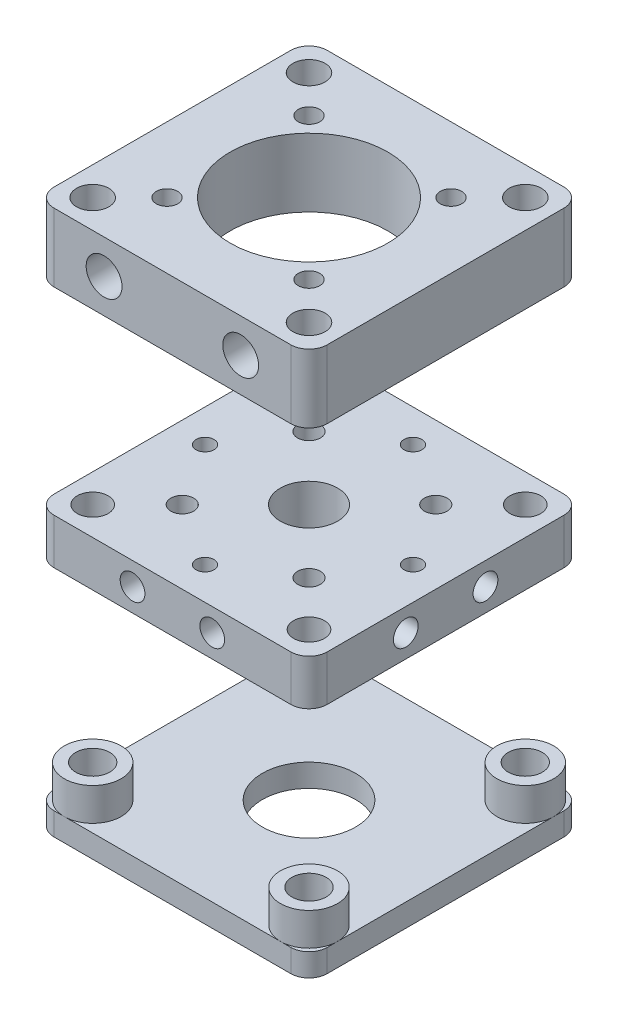
SolidWorks part; units mm, degrees
material "Alum Plate"
ref_plane "Front Plane" through (0, 0, 0) normal (0, 0, 1) x (1, 0, 0)
ref_plane "Top Plane" through (0, 0, 0) normal (0, 1, 0) x (1, 0, 0)
ref_plane "Right Plane" through (0, 0, 0) normal (1, 0, 0) x (0, 0, -1)
other "Bounding Box"
ref_plane "Default Plane" through (-8.9266, -12.7485, 0) normal (-0.1736, 0.9848, 0) x (0.9848, 0.1736, 0)
sketch "Sketch1" plane through (0, 0, 0) normal (0, 1, 0) x (1, 0, 0)
  line L0 (0, -12.5) -> (0, 12.5) construction
  line L1 (-14.5, 0) -> (0, 14.5) construction
  line L2 (-19.05, 19.05) -> (19.05, 19.05)
  line L3 (-19.05, 19.05) -> (-19.05, -19.05)
  line L4 (-19.05, -19.05) -> (19.05, -19.05)
  line L5 (19.05, 19.05) -> (19.05, -19.05)
  line L6 (-19.05, 19.05) -> (19.05, -19.05) construction
  line L7 (-19.05, -19.05) -> (19.05, 19.05) construction
  line L8 (8.8388, 8.8388) -> (-8.8388, 8.8388) construction
  line L9 (8.8388, 8.8388) -> (8.8388, -8.8388) construction
  line L10 (8.8388, -8.8388) -> (-8.8388, -8.8388) construction
  line L11 (-8.8388, 8.8388) -> (-8.8388, -8.8388) construction
  line L12 (8.8388, 8.8388) -> (-8.8388, -8.8388) construction
  line L13 (8.8388, -8.8388) -> (-8.8388, 8.8388) construction
  line L14 (-14.5, 0) -> (0, -14.5) construction
  line L15 (0, 14.5) -> (14.5, 0) construction
  line L16 (0, -14.5) -> (14.5, 0) construction
  line L17 (-14.5, 0) -> (14.5, 0) construction
  line L18 (0, 14.5) -> (0, -14.5) construction
  circle A0 centre (-15.24, 15.24) radius 1.3843 construction
  circle A1 centre (15.24, 15.24) radius 1.3843 construction
  circle A2 centre (15.24, -15.24) radius 1.3843 construction
  circle A3 centre (-15.24, -15.24) radius 1.3843 construction
  circle A4 centre (0, 0) radius 4
  circle A5 centre (8.8388, 8.8388) radius 1.5875
  circle A6 centre (8.8388, -8.8388) radius 1.5875
  circle A7 centre (-8.8388, -8.8388) radius 1.5875
  circle A8 centre (-8.8388, 8.8388) radius 1.5875
  circle A9 centre (-14.5, 0) radius 1.25
  circle A10 centre (0, 14.5) radius 1.25
  circle A11 centre (14.5, 0) radius 1.25
  circle A12 centre (0, -14.5) radius 1.25
  point P3 (0, 0)
  circle B0 centre (-9.8995, -9.8995) radius 1.2645 construction
  circle B1 centre (0, -8) radius 1.5875 construction
  circle B2 centre (0, 0) radius 4 construction
  circle B3 centre (9.8995, 9.8995) radius 1.2645 construction
  circle B4 centre (0, 8) radius 1.5875 construction
  circle B5 centre (9.8995, -9.8995) radius 1.2645 construction
  circle B6 centre (0, -12.5) radius 1.5875 construction
  circle B7 centre (-9.5, 0) radius 1.5875 construction
  circle B8 centre (-15.24, 15.24) radius 1.3843 construction
  circle B9 centre (15.24, 15.24) radius 1.3843 construction
  circle B10 centre (15.24, -15.24) radius 1.3843 construction
  circle B11 centre (-15.24, -15.24) radius 1.3843 construction
  circle B12 centre (9.5, 0) radius 1.5875 construction
  circle B13 centre (-9.8995, 9.8995) radius 1.2645 construction
  circle B14 centre (0, 12.5) radius 1.5875 construction
  dimension "D2" = 3.175
  dimension "D4" = 2.5
  dimension "D1" = 38.1
  dimension "D3" = 25
  dimension "D5" = 29
sketch_block_instance "Block-36mm gearbox motor block holes-1"
sketch_block "Block-36mm gearbox motor block holes"
extrude "Boss-Extrude1" add sketch "Sketch1" along normal mid plane 6.35 contours L5 L2 L3 L4 A12 A11 A9 A8 A10 A7 A6 A5 A4 A3 A2 A1 A0 region at (0, 0, -18.5112)
sketch "Sketch4" plane through (0, 0, 19.05) normal (0, 0, 1) x (1, 0, 0)
  line L0 (-5.5562, 0) -> (0, 0) construction
  line L1 (0, 0) -> (5.5562, 0) construction
  circle A0 centre (-5.5562, 0) radius 1.7272
  circle A1 centre (5.5562, 0) radius 1.7272
  dimension "D2" = 3.4544
  dimension "D1" = 11.1125
extrude "Cut-Extrude2" cut sketch "Sketch4" against normal blind 10.795
sketch "Sketch7" plane through (0, -3.175, 0) normal (0, -1, 0) x (1, 0, 0)
  line L0 (-19.05, 15.0813) -> (-15.0813, 15.0813) construction
  line L1 (-19.05, -19.05) -> (-19.05, 19.05) construction
  line L2 (-15.0813, 15.0813) -> (-15.0813, 19.05) construction
  line L3 (-19.05, 19.05) -> (19.05, 19.05) construction
  line L4 (0, 0) -> (-15.0813, 15.0813) construction
  line L5 (0, 0) -> (15.0813, 15.0812) construction
  circle A0 centre (-15.0813, 15.0813) radius 2.1526
  circle A1 centre (15.0813, 15.0812) radius 2.1527
  circle A2 centre (15.0812, -15.0813) radius 2.1527
  circle A3 centre (-15.0813, -15.0812) radius 2.1526
  dimension "D2" = 4.3053
  dimension "D1" = 3.9688
  dimension "D4" = 90
  dimension "D3" = 4
extrude "Cut-Extrude3" cut sketch "Sketch7" against normal through all
pattern_circular "CirPattern1" count 4 over 360 about axis through (0, 3.175, 0) along (0, -1, 0) of "Cut-Extrude2"
ref_plane "Plane1" through (0, -32.512, 0) normal (0, -1, 0) x (-1, 0, 0)
sketch "Sketch6" plane through (0, -32.512, 0) normal (0, -1, 0) x (-1, 0, 0)
  line L0 (19.05, 19.05) -> (-19.05, 19.05) construction
  line L1 (19.05, 19.05) -> (19.05, -19.05) construction
  line L2 (19.05, -19.05) -> (-19.05, -19.05) construction
  line L3 (-19.05, 19.05) -> (-19.05, -19.05) construction
  line L12 (19.05, 19.05) -> (-19.05, 19.05)
  line L13 (19.05, 19.05) -> (19.05, -19.05)
  line L14 (19.05, -19.05) -> (-19.05, -19.05)
  line L15 (-19.05, 19.05) -> (-19.05, -19.05)
  circle A8 centre (0, 0) radius 6.5
  circle A17 centre (-15.0812, 15.0813) radius 2.1526
  circle A18 centre (15.0813, 15.0812) radius 2.1526
  circle A19 centre (15.0813, -15.0813) radius 2.1527
  circle A20 centre (-15.0813, -15.0812) radius 2.1526
  circle A21 centre (-15.0812, 15.0813) radius 2.1527 construction
  dimension "D2" = 13
extrude "Boss-Extrude2" add sketch "Sketch6" along normal blind 3.175 separate body
fillet "Fillet1" radius 2.54 4 edges at (-19.05, 0, 19.05) (-19.05, 0, -19.05) (19.05, 0, -19.05) (19.05, 0, 19.05)
fillet "Fillet2" radius 2.54 4 edges at (-19.05, -34.0995, 19.05) (-19.05, -34.0995, -19.05) (19.05, -34.0995, -19.05) (19.05, -34.0995, 19.05)
sketch "Sketch8" plane through (0, -32.512, 0) normal (0, 1, 0) x (1, 0, 0)
  line L0 (-16.51, 19.05) -> (16.51, 19.05) construction
  circle A0 centre (-15.0813, 15.0812) radius 2.3876
  circle A1 centre (-15.0813, 15.0812) radius 3.9688
  dimension "D1" = 4.7752
extrude "Boss-Extrude3" add sketch "Sketch8" along normal offset from surface (4.572 mm away) 24.765 separate body up to face at (-15.0813, -3.175, -17.2339)
pattern_circular "CirPattern2" count 4 over 360 about axis through (0, -35.687, 0) along (0, 1, 0) of bodies 110
delete or keep bodies "Body-Delete/Keep 1" [suppressed] type keep bodies bodies 108
delete or keep bodies "Body-Delete/Keep 2" [suppressed] type keep bodies bodies 107
delete or keep bodies "Body-Delete/Keep 3" [suppressed] bodies 113
delete or keep bodies "Body-Delete/Keep 4" [suppressed] type delete bodies bodies 107
sketch "Sketch9" plane through (0, 3.175, 0) normal (0, 1, 0) x (1, 0, 0)
  line L0 (-16.51, -19.05) -> (16.51, -19.05) construction
  line L1 (-19.05, 19.05) -> (19.05, 19.05)
  line L2 (-19.05, 19.05) -> (-19.05, -19.05)
  line L3 (-19.05, -19.05) -> (19.05, -19.05)
  line L4 (19.05, 19.05) -> (19.05, -19.05)
  line L5 (-19.05, 19.05) -> (19.05, -19.05) construction
  line L6 (-19.05, -19.05) -> (19.05, 19.05) construction
  point P0 (0, 0)
extrude "Boss-Extrude4" add sketch "Sketch9" along normal blind 9.525 from offset 27.559 separate body
sketch "Sketch12" plane through (0, 0, -19.05) normal (0, 0, -1) x (-1, 0, 0)
  line L0 (-19.05, 35.4965) -> (-9.525, 35.4965) construction
  line L1 (-19.05, 40.259) -> (-19.05, 30.734) construction
  line L2 (-9.525, 35.4965) -> (9.525, 35.4965) construction
  line L3 (9.525, 35.4965) -> (19.05, 35.4965) construction
  line L4 (19.05, 40.259) -> (19.05, 30.734) construction
  circle A0 centre (-9.525, 35.4965) radius 2.5
  circle A1 centre (9.525, 35.4965) radius 2.5
  dimension "D2" = 5
  dimension "D1" = 19.05
extrude "Cut-Extrude5" cut sketch "Sketch12" against normal blind 9.525
mirror "Mirror1" about plane through (0, 0, 0) normal (0, 0, 1) of "Cut-Extrude5"
fillet "Fillet3" radius 2.54 4 edges at (19.05, 35.4965, -19.05) (19.05, 35.4965, 19.05) (-19.05, 35.4965, 19.05) (-19.05, 35.4965, -19.05)
sketch "Sketch10" plane through (0, 40.259, 0) normal (0, 1, 0) x (1, 0, 0)
  line L1 (-9.8995, 9.8995) -> (9.8995, 9.8995) construction
  line L2 (-9.8995, 9.8995) -> (-9.8995, -9.8995) construction
  line L3 (-9.8995, -9.8995) -> (9.8995, -9.8995) construction
  line L4 (9.8995, 9.8995) -> (9.8995, -9.8995) construction
  line L5 (-9.8995, 9.8995) -> (9.8995, -9.8995) construction
  line L6 (-9.8995, -9.8995) -> (9.8995, 9.8995) construction
  line L7 (-15.0813, 15.0812) -> (15.0813, 15.0812) construction
  line L8 (-15.0813, 15.0812) -> (-15.0813, -15.0813) construction
  line L9 (-15.0813, -15.0813) -> (15.0813, -15.0813) construction
  line L10 (15.0813, 15.0812) -> (15.0813, -15.0813) construction
  line L11 (-15.0813, 15.0812) -> (15.0813, -15.0813) construction
  line L12 (-15.0813, -15.0813) -> (15.0813, 15.0812) construction
  circle A0 centre (0, 0) radius 11
  circle A1 centre (-9.8995, 9.8995) radius 1.5
  circle A2 centre (9.8995, 9.8995) radius 1.5
  circle A3 centre (9.8995, -9.8995) radius 1.5
  circle A4 centre (-9.8995, -9.8995) radius 1.5
  circle A5 centre (-15.0813, -15.0813) radius 2.2479
  circle A6 centre (-15.0813, 15.0812) radius 2.2479
  circle A7 centre (15.0813, 15.0812) radius 2.2479
  circle A8 centre (15.0813, -15.0813) radius 2.2479
  dimension "D2" = 22
  dimension "D4" = 4.4958
  dimension "D5" = 3
  dimension "D1" = 28
  dimension "D3" = 30.1625
extrude "Cut-Extrude4" cut sketch "Sketch10" against normal through all
